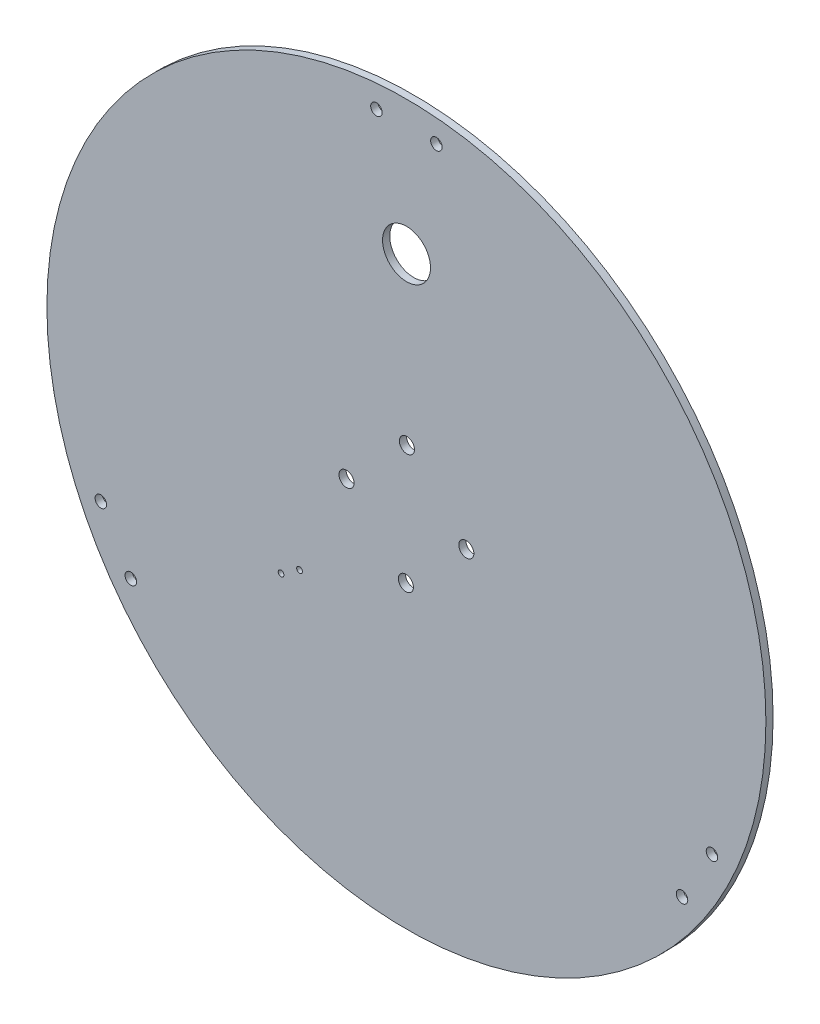
SolidWorks part; units mm, degrees
ref_plane "Front Plane" through (0, 0, 0) normal (0, 0, 1) x (1, 0, 0)
ref_plane "Top Plane" through (0, 0, 0) normal (0, 1, 0) x (1, 0, 0)
ref_plane "Right Plane" through (0, 0, 0) normal (1, 0, 0) x (0, 0, -1)
sketch "Sketch1" plane through (0, 0, 0) normal (0, 0, 1) x (1, 0, 0)
  line L0 (0, 0) -> (0, 140) construction
  line L1 (0, 140) -> (0, 150) construction
  line L2 (-12.5, 140) -> (12.5, 140) construction
  circle A0 centre (0, 0) radius 150
  circle A1 centre (12.5, 140) radius 2.4
  circle A2 centre (-12.5, 140) radius 2.4
  circle A3 centre (127.4936, -59.1747) radius 2.4
  circle A4 centre (114.9936, -80.8253) radius 2.4
  circle A5 centre (-114.9936, -80.8253) radius 2.4
  circle A6 centre (-127.4936, -59.1747) radius 2.4
  circle A7 centre (0.0487, 94) radius 10
  circle A10 centre (-44.588, -42.5012) radius 1.2
  circle A11 centre (-52.288, -47.6012) radius 1.2
  circle A14 centre (24.9991, -0.2153) radius 3.15
  circle A15 centre (-0.2153, -24.9991) radius 3.15
  circle A16 centre (-24.9991, 0.2153) radius 3.15
  circle A17 centre (0.2153, 24.9991) radius 3.15
  point P9 (0, 140)
  point P12 (0, 0)
  point P21 (0, 0)
  dimension "D1" = 300
  dimension "D2" = 3
  dimension "D4" = 4.8
  dimension "D6" = 20
  dimension "D7" = 2.4
  dimension "D8" = 2.4
  dimension "D9" = 6.3
  dimension "D10" = 6.3
  dimension "D11" = 6.3
  dimension "D12" = 6.3
  dimension "D3" = 25
  dimension "D5" = 140
extrude "Boss-Extrude2" add sketch "Sketch1" along normal blind 3
